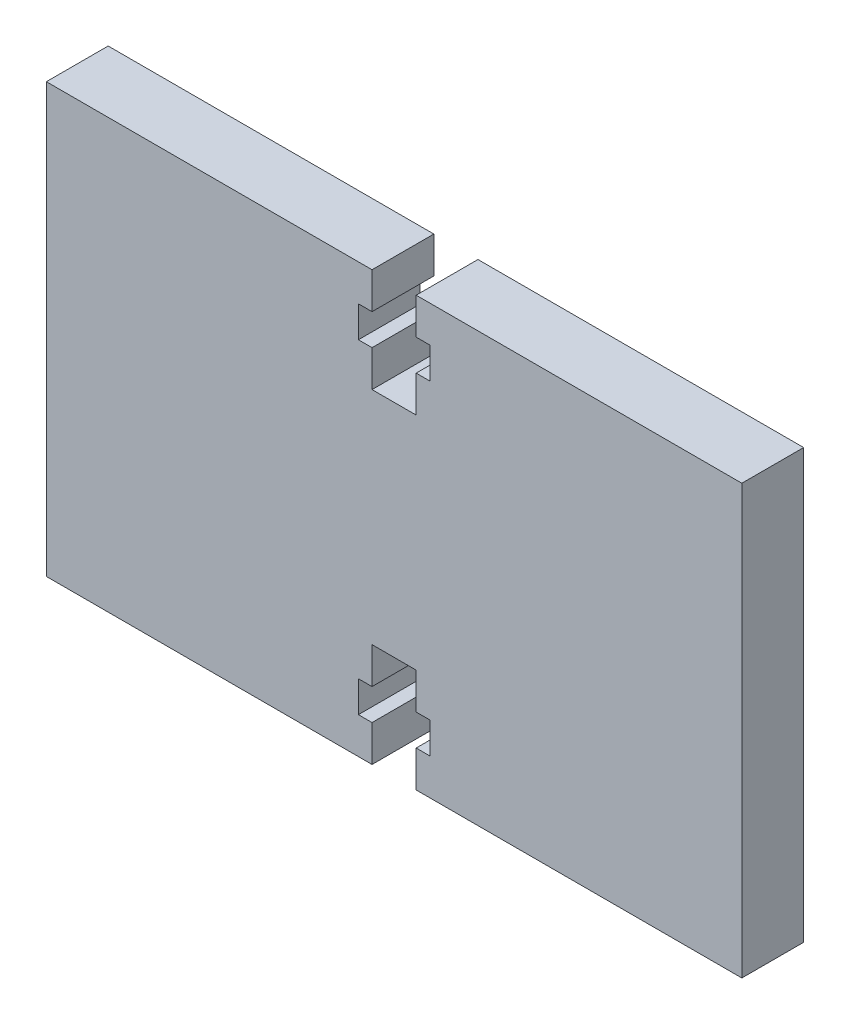
SolidWorks part; units mm, degrees
ref_plane "Front Plane" through (0, 0, 0) normal (0, 0, 1) x (1, 0, 0)
ref_plane "Top Plane" through (0, 0, 0) normal (0, 1, 0) x (1, 0, 0)
ref_plane "Right Plane" through (0, 0, 0) normal (1, 0, 0) x (0, 0, -1)
sketch "Sketch1" plane through (0, 0, 0) normal (0, 0, 1) x (1, 0, 0)
  line L0 (0, 16.51) -> (0, -7.29) construction
  line L1 (1.7, -16.51) -> (1.7, -13.71)
  line L2 (-26.797, -16.51) -> (-26.797, 16.51)
  line L3 (-26.797, 16.51) -> (-1.7, 16.51)
  line L4 (26.797, -16.51) -> (26.797, 16.51)
  line L5 (-26.797, -16.51) -> (26.797, 16.51) construction
  line L6 (-26.797, 16.51) -> (26.797, -16.51) construction
  line L7 (-13.4509, -7.29) -> (13.4509, -7.29) construction
  line L8 (0, 5.91) -> (26.797, 5.91) construction
  line L9 (-1.7, 16.51) -> (-1.7, 13.71)
  line L10 (-1.7, 13.71) -> (-2.75, 13.71)
  line L11 (-2.75, 13.71) -> (-2.75, 11.31)
  line L12 (-2.75, 11.31) -> (-1.7, 11.31)
  line L13 (-1.7, 11.31) -> (-1.7, 8.51)
  line L14 (-1.7, 8.51) -> (1.7, 8.51)
  line L15 (-2.75, 12.51) -> (0, 12.51) construction
  line L16 (1.7, 11.31) -> (1.7, 8.51)
  line L17 (2.75, 11.31) -> (1.7, 11.31)
  line L18 (2.75, 13.71) -> (2.75, 11.31)
  line L19 (1.7, 13.71) -> (2.75, 13.71)
  line L20 (1.7, 16.51) -> (1.7, 13.71)
  line L21 (1.7, 16.51) -> (26.797, 16.51)
  line L22 (0, 0) -> (26.797, 0) construction
  line L23 (1.7, -13.71) -> (2.75, -13.71)
  line L24 (2.75, -13.71) -> (2.75, -11.31)
  line L25 (2.75, -11.31) -> (1.7, -11.31)
  line L26 (1.7, -11.31) -> (1.7, -8.51)
  line L27 (-1.7, -8.51) -> (1.7, -8.51)
  line L28 (-1.7, -11.31) -> (-1.7, -8.51)
  line L29 (-2.75, -11.31) -> (-1.7, -11.31)
  line L30 (-2.75, -13.71) -> (-2.75, -11.31)
  line L31 (-1.7, -13.71) -> (-2.75, -13.71)
  line L32 (-1.7, -16.51) -> (-1.7, -13.71)
  line L33 (1.7, -16.51) -> (26.797, -16.51)
  line L34 (-26.797, -16.51) -> (-1.7, -16.51)
  point P0 (0, 0)
  point P23 (0, 8.51)
  dimension "D1" = 33.02
  dimension "D2" = 53.594
  dimension "D3" = 1.7
  dimension "D4" = 2.75
  dimension "D5" = 8
  dimension "D6" = 4
  dimension "D7" = 2.4
extrude "Boss-Extrude1" add sketch "Sketch1" along normal blind 4.7625 contours L4 L21 L20 L19 L18 L17 L16 L14 L13 L12 L11 L10 L9 L3 L2 region at (0, 0, 0)
equation "\"D6@Sketch1\"=\"D5@Sketch1\"/2"
